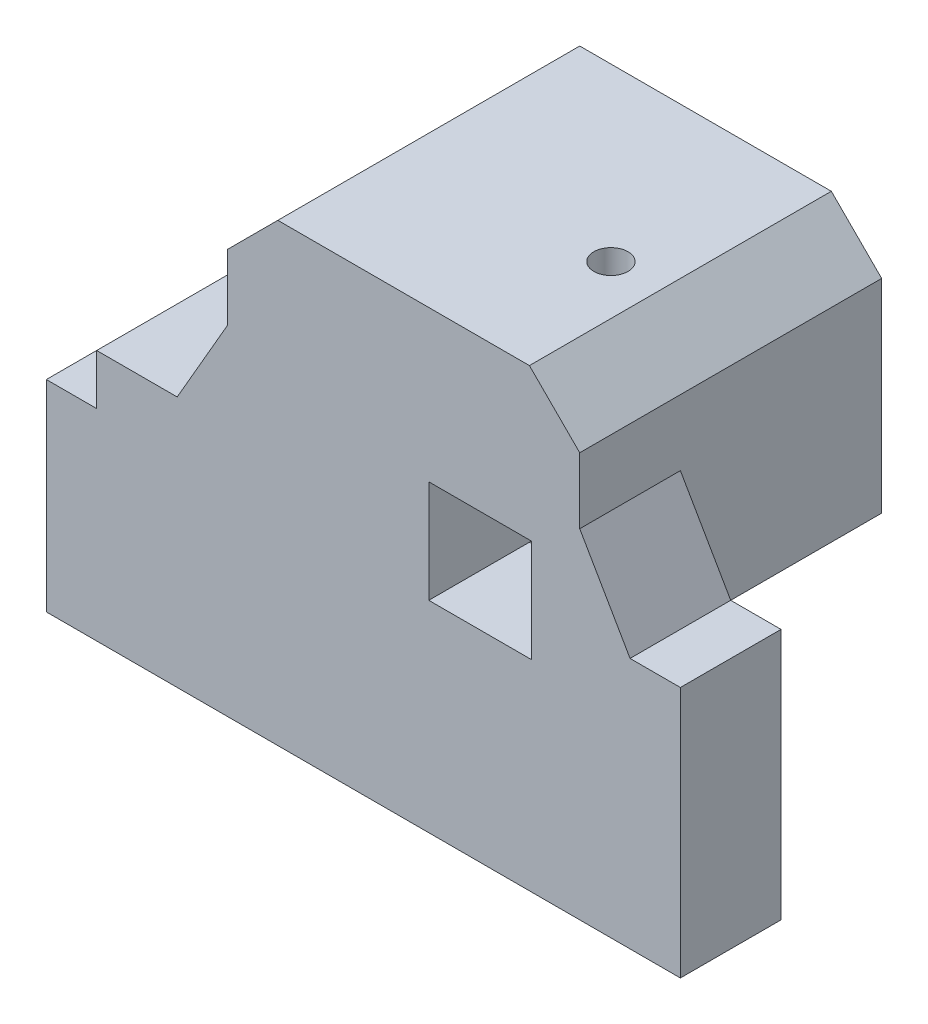
SolidWorks part; units mm, degrees
material "ABS"
ref_plane "Płaszczyzna przednia" through (0, 0, 0) normal (0, 0, 1) x (1, 0, 0)
ref_plane "Płaszczyzna górna" through (0, 0, 0) normal (0, 1, 0) x (1, 0, 0)
ref_plane "Płaszczyzna prawa" through (0, 0, 0) normal (1, 0, 0) x (0, 0, -1)
sketch "Szkic1" plane through (0, 0, 0) normal (0, 0, 1) x (1, 0, 0)
  line L1 (-29, -10) -> (29, -10)
  line L2 (-29, -10) -> (-29, 10)
  line L3 (-29, 10) -> (29, 10)
  line L4 (29, -10) -> (29, 10)
  line L5 (-29, -10) -> (29, 10) construction
  line L6 (-29, 10) -> (29, -10) construction
  point P0 (0, 0)
  dimension "D1" = 20
  dimension "D2" = 58
extrude "Dodanie-wyciągnięcie1" add sketch "Szkic1" along normal blind 5
sketch "Szkic2" plane through (29, 0, 0) normal (1, 0, 0) x (0, 0, -1)
  line L0 (0, 15) -> (-10, 15)
  line L1 (0, 10) -> (5, 10)
  line L2 (0, 10) -> (0, 15)
  line L3 (0, 15) -> (5, 15)
  line L4 (5, 10) -> (5, 15)
  line L5 (-5, 10) -> (0, 10)
  line L6 (-10, 15) -> (-10, 10)
  line L7 (-10, 10) -> (-5, 10)
  line M2 (0, 10) -> (-5, 10)
  dimension "D1" = 5
  dimension "D2" = 5
extrude "Dodanie-wyciągnięcie2" add sketch "Szkic2" against normal up to surface (58 mm away) contours L2 M2 | L1 L4 L3 L2 region at (29, 12.5, 5) region at (29, 12.5, -2.5) up to face at (-29, 0, 2.5)
sketch "Szkic3" plane through (0, -10, 0) normal (0, -1, 0) x (1, 0, 0)
  line L0 (-29, 0) -> (-34, 5)
  line L1 (-29, 5) -> (-29, 0) construction
  line L2 (-29, 0) -> (-34, 0) construction
  line L3 (-34, 5) -> (-34, 10)
  line L4 (-34, 10) -> (-29, 10)
  line L5 (-29, 10) -> (-24, 5)
  line L6 (-29, 5) -> (29, 5) construction
  line L7 (-29, 5) -> (29, 5)
  line L8 (-29, 5) -> (-29, 0)
  line M7 (29, 5) -> (-29, 5)
  line M8 (-29, 5) -> (-29, 0)
  dimension "D1" = 45
  dimension "D2" = 5
  dimension "D3" = 5
extrude "Dodanie-wyciągnięcie3" add sketch "Szkic3" against normal blind 20 contours L5 L4 L3 L0 M8 M7 region at (-30.25, -10, 6.25)
sketch "Szkic5" plane through (0, 0, 5) normal (0, 0, 1) x (1, 0, 0)
  line L0 (-34, 10) -> (-34, -10) construction
  line L1 (14.2, 10) -> (4, 10)
  line L2 (14.2, 10) -> (14.2, 20.2)
  line L3 (14.2, 20.2) -> (4, 20.2)
  line L4 (4, 10) -> (4, 20.2)
  line L5 (14.2, 10) -> (4, 20.2) construction
  line L6 (14.2, 20.2) -> (4, 10) construction
  line L7 (29, 10) -> (-24, 10) construction
  line L8 (29, 10) -> (-24, 10) construction
  line L10 (-16, 10) -> (19, 10)
  line L11 (-16, 10) -> (-16, 35.2)
  line L12 (-16, 35.2) -> (19, 35.2)
  line L13 (19, 10) -> (19, 35.2)
  point P0 (9.1, 15.1)
  dimension "D1" = 10.2
  dimension "D2" = 38
  dimension "D3" = 15
  dimension "D4" = 20
  dimension "D5" = 4.8
extrude "Dodanie-wyciągnięcie4" add sketch "Szkic5" against normal blind 10 contours L13 L12 L11 L4 L3 L2 region at (0.4836, 23.603, 5)
extrude "Wytnij-wyciągnięcie2" cut sketch "Szkic5<3>" against normal through all and the other way through all contours L4 L2 L3 region at (9.1, 15.1, 5)
sketch "Szkic5<3>" plane through (0, 0, 5) normal (0, 0, 1) x (1, 0, 0) same geometry as "Szkic5"
sketch "Szkic6" plane through (0, 10, 0) normal (0, 1, 0) x (1, 0, 0)
  line L1 (-29, -10) -> (29, -10)
  line L2 (-29, -10) -> (-29, -5)
  line L3 (-29, -5) -> (29, -5)
  line L4 (29, -10) -> (29, -5)
  line L5 (29, -5) -> (14.2, -5) construction
  dimension "D1" = 5
  dimension "D2" = 58
extrude "Dodanie-wyciągnięcie5" add sketch "Szkic6" against normal blind 20
sketch "Szkic7" plane through (0, -10, 0) normal (0, -1, 0) x (1, 0, 0)
  line L0 (-34, 10) -> (29, 10) construction
  line L1 (-34, 5) -> (-34, 10) construction
  circle A0 centre (-19, 5) radius 2
  circle A1 centre (11, 5) radius 2
  dimension "D1" = 4
  dimension "D2" = 5
  dimension "D3" = 15
  dimension "D4" = 30
extrude "Wytnij-wyciągnięcie3" cut sketch "Szkic7" against normal blind 10
sketch "Szkic10" plane through (0, 0, -5) normal (0, 0, -1) x (-1, 0, 0)
  line L0 (16, 15) -> (16, 10)
  line L10 (-4, 20.2) -> (-4, 10)
  line L11 (-4, 10) -> (29, 10)
  line L12 (29, 10) -> (29, 15)
  line L13 (29, 15) -> (16, 15)
  line L14 (16, 15) -> (16, 35.2)
  line L15 (16, 35.2) -> (-19, 35.2)
  line L16 (-19, 35.2) -> (-19, 15)
  line L17 (-29, 10) -> (-14.2, 10)
  line L18 (-14.2, 10) -> (-14.2, 20.2)
  line L19 (-14.2, 20.2) -> (-4, 20.2)
  line L20 (-4, 20.2) -> (-4, 10)
  line L21 (-4, 10) -> (29, 10)
  line L22 (29, 10) -> (29, 15)
  line L23 (29, 15) -> (16, 15)
  line L24 (16, 15) -> (16, 35.2)
  line L25 (16, 35.2) -> (-19, 35.2)
  line L26 (-19, 35.2) -> (-19, 15)
  line L27 (-29, 10) -> (-14.2, 10)
  line L28 (-14.2, 10) -> (-14.2, 20.2)
  line L29 (-14.2, 20.2) -> (-4, 20.2)
  line L33 (-19, 15) -> (-29, 15)
  line L34 (-19, 15) -> (-29, 15)
  line L35 (-29, 15) -> (-29, 10)
  line L36 (-29, 15) -> (-29, 10)
  line M11 (-4, 20.2) -> (-4, 10)
  line M12 (-4, 10) -> (29, 10)
  line M15 (16, 15) -> (16, 35.2)
  line M16 (16, 35.2) -> (-19, 35.2)
  line M17 (-19, 35.2) -> (-19, 15)
  line M18 (-29, 10) -> (-14.2, 10)
  line M19 (-14.2, 10) -> (-14.2, 20.2)
  line M20 (-14.2, 20.2) -> (-4, 20.2)
  dimension "D1" = 0
extrude "Dodanie-wyciągnięcie8" add sketch "Szkic10" along normal blind 10 contours L0 M15 M16 M17 M18 M19 M20 M11 M12 region at (1.9038, 22.9325, -5)
sketch "Szkic11" plane through (0, 0, -15) normal (0, 0, -1) x (-1, 0, 0)
  line L0 (-14.2, 10) -> (-4, 10)
  line L8 (16, 10) -> (16, 35.2)
  line L9 (16, 35.2) -> (-19, 35.2)
  line L10 (-19, 35.2) -> (-19, 15)
  line L11 (-29, 10) -> (-14.2, 10)
  line L12 (-14.2, 10) -> (-14.2, 20.2)
  line L13 (-14.2, 20.2) -> (-4, 20.2)
  line L14 (-4, 20.2) -> (-4, 10)
  line L15 (-4, 10) -> (16, 10)
  line L16 (16, 10) -> (16, 35.2)
  line L17 (16, 35.2) -> (-19, 35.2)
  line L18 (-19, 35.2) -> (-19, 15)
  line L19 (-29, 10) -> (-14.2, 10)
  line L20 (-14.2, 10) -> (-14.2, 20.2)
  line L21 (-14.2, 20.2) -> (-4, 20.2)
  line L22 (-4, 20.2) -> (-4, 10)
  line L23 (-4, 10) -> (16, 10)
  line L27 (-19, 15) -> (-29, 15)
  line L28 (-19, 15) -> (-29, 15)
  line L29 (-29, 15) -> (-29, 10)
  line L30 (-29, 15) -> (-29, 10)
  line M9 (16, 10) -> (16, 35.2)
  line M10 (16, 35.2) -> (-19, 35.2)
  line M11 (-19, 35.2) -> (-19, 15)
  line M12 (-29, 10) -> (-14.2, 10)
  line M13 (-14.2, 10) -> (-14.2, 20.2)
  line M14 (-14.2, 20.2) -> (-4, 20.2)
  line M15 (-4, 20.2) -> (-4, 10)
  line M16 (-4, 10) -> (16, 10)
  dimension "D1" = 0
extrude "Dodanie-wyciągnięcie9" add sketch "Szkic11" along normal blind 5 contours M16 M9 M10 M11 M12 M13 M14 M15 | L0 M13 M15 M14 region at (9.1, 15.1, -15) region at (1.9038, 22.9325, -15)
chamfer "Sfazowanie2" distance 5 angle 45 2 edges at (19, 35.2, -7.5) (-16, 35.2, -7.5)
sketch "Szkic12" plane through (0, 10, 0) normal (0, -1, 0) x (1, 0, 0)
  line L0 (19, 5) -> (19, -20) construction
  line L1 (29, 0) -> (14.2, 0) construction
  line L2 (19, 5) -> (19, -20)
  line L3 (29, 0) -> (14.2, 0)
  line L4 (29, -20) -> (-16, -20) construction
  line L5 (29, 0) -> (29, -20) construction
  line L6 (29, -20) -> (-16, -20)
  line L7 (29, 0) -> (29, -20)
  line M8 (-16, -20) -> (29, -20)
  line M9 (29, -20) -> (29, 0)
  line M10 (29, 0) -> (14.2, 0)
extrude "Wytnij-wyciągnięcie4" cut sketch "Szkic12" against normal blind 10 contours L2 M10 M8 M9 region at (24, 10, -10)
sketch "Szkic13" plane through (0, 35.2, 0) normal (0, 1, 0) x (1, 0, 0)
  line L0 (9.1, 0) -> (9.1, 2.4524) construction
  line L4 (-11, -5) -> (14, -5)
  line L5 (14, -5) -> (14, 20)
  line L6 (14, 20) -> (-11, 20)
  line L7 (-11, 20) -> (-11, -5)
  line L8 (-11, -5) -> (14, -5) construction
  line L9 (14, -5) -> (14, 20) construction
  line L10 (14, 20) -> (-11, 20) construction
  line L11 (-11, 20) -> (-11, -5) construction
  line L12 (4, 0) -> (4, -10)
  line L13 (4, -10) -> (14.2, -10)
  line L14 (14.2, -10) -> (14.2, 0)
  line L15 (14.2, 0) -> (4, 0)
  line L16 (4, 0) -> (4, -10) construction
  line L17 (4, -10) -> (14.2, -10) construction
  line L18 (14.2, -10) -> (14.2, 0) construction
  line L19 (14.2, 0) -> (4, 0) construction
  circle A0 centre (9.1, 3) radius 1.7
  point P10 (0, 0)
  dimension "D3" = 3.4
  dimension "D4" = 8
  dimension "D1" = 0
  dimension "D2" = 0
extrude "Wytnij-wyciągnięcie5" cut sketch "Szkic13" against normal through all
sketch "Szkic15" plane through (0, 0, 5) normal (0, 0, 1) x (1, 0, 0)
  line L10 (19, 15) -> (19, 30.2)
  line L11 (19, 30.2) -> (14, 35.2)
  line L12 (14, 35.2) -> (-11, 35.2)
  line L13 (-11, 35.2) -> (-16, 30.2)
  line L14 (-16, 30.2) -> (-16, 15)
  line L15 (-16, 15) -> (4, 15)
  line L16 (4, 15) -> (4, 20.2)
  line L17 (4, 20.2) -> (14.2, 20.2)
  line L18 (14.2, 20.2) -> (14.2, 15)
  line L19 (14.2, 15) -> (19, 15)
  line L20 (19, 15) -> (19, 30.2)
  line L21 (19, 30.2) -> (14, 35.2)
  line L22 (14, 35.2) -> (-11, 35.2)
  line L23 (-11, 35.2) -> (-16, 30.2)
  line L24 (-16, 30.2) -> (-16, 15)
  line L25 (-16, 15) -> (4, 15)
  line L26 (4, 15) -> (4, 20.2)
  line L27 (4, 20.2) -> (14.2, 20.2)
  line L28 (14.2, 20.2) -> (14.2, 15)
  line L29 (14.2, 15) -> (19, 15)
  dimension "D1" = 0
extrude "Dodanie-wyciągnięcie11" add sketch "Szkic15" along normal blind 5
chamfer "Sfazowanie6" distance 5 angle 60 2 edges at (19, 15, 5) (-16, 15, 2.5) first distance on face at (24, 15, 5) first distance on face at (-22.5, 15, 2.5)
